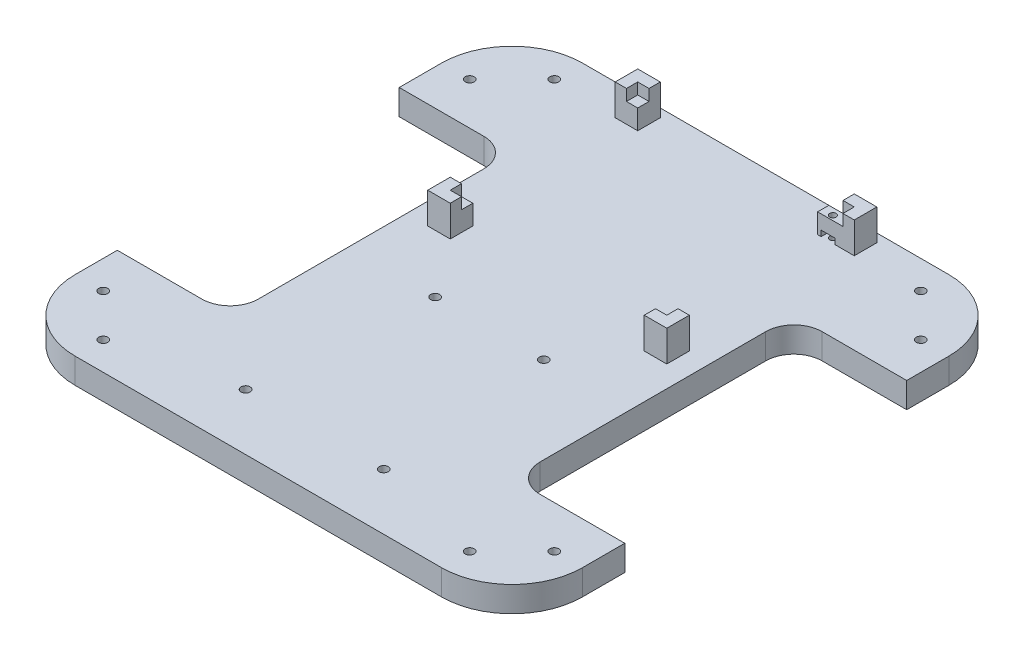
SolidWorks part; units mm, degrees
ref_plane "Front Plane" through (0, 0, 0) normal (0, 0, 1) x (1, 0, 0)
ref_plane "Top Plane" through (0, 0, 0) normal (0, 1, 0) x (1, 0, 0)
ref_plane "Right Plane" through (0, 0, 0) normal (1, 0, 0) x (0, 0, -1)
sketch "Sketch1" plane through (0, 0, 0) normal (0, 1, 0) x (1, 0, 0)
  line L1 (-65, -90) -> (65, -90)
  line L2 (-90, -65) -> (-90, 65)
  line L3 (-65, 90) -> (65, 90)
  line L4 (90, -65) -> (90, 65)
  arc A0 (-90, 65) -> (-65, 90) centre (-65, 65) cw
  arc A1 (65, 90) -> (90, 65) centre (65, 65) cw
  arc A2 (90, -65) -> (65, -90) centre (65, -65) cw
  arc A3 (-65, -90) -> (-90, -65) centre (-65, -65) cw
  point P4 (-90, 0)
  point P6 (0, 90)
  dimension "D3" = 25
  dimension "D1" = 180
  dimension "D2" = 180
extrude "Plate" add sketch "Sketch1" along normal blind 9
sketch "Sketch3" plane through (0, 9, 0) normal (0, 1, 0) x (1, 0, 0)
  line L0 (-65, 90) -> (-65, -90) construction
  line L1 (65, 90) -> (65, -90) construction
  line L2 (-90, 65) -> (90, 65) construction
  line L3 (-90, -65) -> (90, -65) construction
  circle A0 centre (-65, 80) radius 1.6
  circle A1 centre (-80, 65) radius 1.6
  circle A2 centre (80, 65) radius 1.6
  circle A3 centre (80, -65) radius 1.6
  circle A4 centre (65, 80) radius 1.6
  circle A5 centre (65, -80) radius 1.6
  circle A6 centre (-65, -80) radius 1.6
  circle A7 centre (-80, -65) radius 1.6
  dimension "D1" = 3.2
  dimension "D2" = 15
  dimension "D3" = 15
  dimension "D4" = 15
  dimension "D5" = 15
  dimension "D6" = 15
  dimension "D7" = 15
  dimension "D8" = 15
  dimension "D9" = 15
extrude "Hex Holes" cut sketch "Sketch3" against normal through all
sketch "Sketch4" plane through (0, 9, 0) normal (0, 1, 0) x (1, 0, 0)
  line L0 (-90, -65) -> (-90, 65) construction
  line L1 (-65, -90) -> (65, -90) construction
  circle A0 centre (-24.5, -70) radius 1.6
  circle A1 centre (24.5, -70) radius 1.6
  circle A2 centre (-19.25, -8) radius 1.6
  circle A3 centre (19.25, -8) radius 1.6
  dimension "D1" = 3.2
  dimension "D2" = 62
  dimension "D3" = 49
  dimension "D4" = 5.25
  dimension "D5" = 38.5
  dimension "D6" = 65.5
  dimension "D7" = 20
extrude "Arduino Holes" cut sketch "Sketch4" against normal through all
sketch "Sketch5" plane through (0, 9, 0) normal (0, 1, 0) x (1, 0, 0)
  line L0 (-90, -65) -> (-90, 65) construction
  line L1 (-90, -50) -> (-50, -50)
  line L2 (-90, -50) -> (-90, 50)
  line L3 (-90, 50) -> (-50, 50)
  line L4 (-50, -50) -> (-50, 50)
  line L5 (90, -65) -> (90, 65) construction
  line L6 (90, -50) -> (50, -50)
  line L7 (90, -50) -> (90, 50)
  line L8 (90, 50) -> (50, 50)
  line L9 (50, -50) -> (50, 50)
  line L10 (-90, 0) -> (90, 0) construction
  point P14 (-90, 0)
  point P15 (90, 0)
  dimension "D1" = 100
  dimension "D3" = 40
extrude "Cut-Extrude1" cut sketch "Sketch5" against normal through all
fillet "Fillet1" radius 10 4 edges at (50, 4.5, -50) (50, 4.5, 50) (-50, 4.5, -50) (-50, 4.5, 50)
sketch "Sketch6" plane through (0, 9, 0) normal (0, 1, 0) x (1, 0, 0)
  line L0 (-65, 90) -> (65, 90) construction
  line L1 (-38.4, 16.5) -> (38.4, 16.5) construction
  line L2 (-38.4, 16.5) -> (-38.4, 83) construction
  line L3 (-38.4, 83) -> (38.4, 83) construction
  line L4 (38.4, 16.5) -> (38.4, 83) construction
  line L5 (34.4, 83) -> (38.4, 83)
  line L6 (38.4, 83) -> (38.4, 79)
  line L7 (38.4, 79) -> (42.4, 79)
  line L8 (42.4, 79) -> (42.4, 87)
  line L9 (42.4, 87) -> (34.4, 87)
  line L10 (34.4, 87) -> (34.4, 83)
  line L11 (38.4, 20.5) -> (38.4, 16.5)
  line L12 (38.4, 16.5) -> (34.4, 16.5)
  line L13 (34.4, 16.5) -> (34.4, 12.5)
  line L14 (34.4, 12.5) -> (42.4, 12.5)
  line L15 (42.4, 12.5) -> (42.4, 20.5)
  line L16 (42.4, 20.5) -> (38.4, 20.5)
  line L17 (-38.4, 16.5) -> (-34.4, 16.5)
  line L18 (-34.4, 16.5) -> (-34.4, 12.5)
  line L19 (-34.4, 12.5) -> (-42.4, 12.5)
  line L20 (-42.4, 12.5) -> (-42.4, 20.5)
  line L21 (-42.4, 20.5) -> (-38.4, 20.5)
  line L22 (-38.4, 20.5) -> (-38.4, 16.5)
  line L23 (-38.4, 83) -> (-34.4, 83)
  line L24 (-34.4, 83) -> (-34.4, 87)
  line L25 (-34.4, 87) -> (-42.4, 87)
  line L26 (-42.4, 87) -> (-42.4, 79)
  line L27 (-42.4, 79) -> (-38.4, 79)
  line L28 (-38.4, 79) -> (-38.4, 83)
  point P6 (0, 90)
  point P7 (0, 83)
  dimension "D1" = 66.5
  dimension "D2" = 76.8
  dimension "D3" = 7
  dimension "D4" = 4
extrude "Boss-Extrude1" add sketch "Sketch6" along normal blind 11
sketch "Sketch7" plane through (0, 9, 0) normal (0, 1, 0) x (1, 0, 0)
  line L1 (-38.4, 16.5) -> (-34.4, 16.5)
  line L2 (-38.4, 16.5) -> (-38.4, 20.5)
  line L3 (-38.4, 20.5) -> (-34.4, 20.5)
  line L4 (-34.4, 16.5) -> (-34.4, 20.5)
  line L5 (38.4, 16.5) -> (34.4, 16.5)
  line L6 (38.4, 16.5) -> (38.4, 20.5)
  line L7 (38.4, 20.5) -> (34.4, 20.5)
  line L8 (34.4, 16.5) -> (34.4, 20.5)
  line L9 (-38.4, 83) -> (-34.4, 83)
  line L10 (-38.4, 83) -> (-38.4, 79)
  line L11 (-38.4, 79) -> (-34.4, 79)
  line L12 (-34.4, 83) -> (-34.4, 79)
  line L13 (38.4, 83) -> (29.4, 83)
  line L14 (38.4, 83) -> (38.4, 79)
  line L15 (38.4, 79) -> (29.4, 79)
  line L16 (29.4, 83) -> (29.4, 79)
  dimension "D1" = 4
  dimension "D2" = 4
  dimension "D3" = 9
extrude "Boss-Extrude2" add sketch "Sketch7" along normal blind 7
sketch "Sketch8" plane through (0, 16, 0) normal (0, 1, 0) x (1, 0, 0)
  line L0 (38.4, 83) -> (34.4, 83) construction
  line L1 (38.4, 79) -> (38.4, 83) construction
  circle A0 centre (33.15, 80.65) radius 1.15
  dimension "D1" = 2.3
  dimension "D2" = 2.35
  dimension "D3" = 5.25
extrude "Cut-Extrude2" cut sketch "Sketch8" against normal through all
sketch "Sketch9" plane through (0, 0, -79) normal (0, 0, 1) x (1, 0, 0)
  line L0 (29.4, 9) -> (42.4, 9) construction
  line L1 (30.65, 11) -> (35.65, 11)
  line L2 (30.65, 11) -> (30.65, 9)
  line L3 (30.65, 9) -> (35.65, 9)
  line L4 (35.65, 11) -> (35.65, 9)
  line L6 (29.4, 16) -> (29.4, 9) construction
  point P6 (33.15, 11)
  dimension "D1" = 5
  dimension "D2" = 2
  dimension "D3" = 3.75
extrude "Cut-Extrude3" cut sketch "Sketch9" against normal through all
